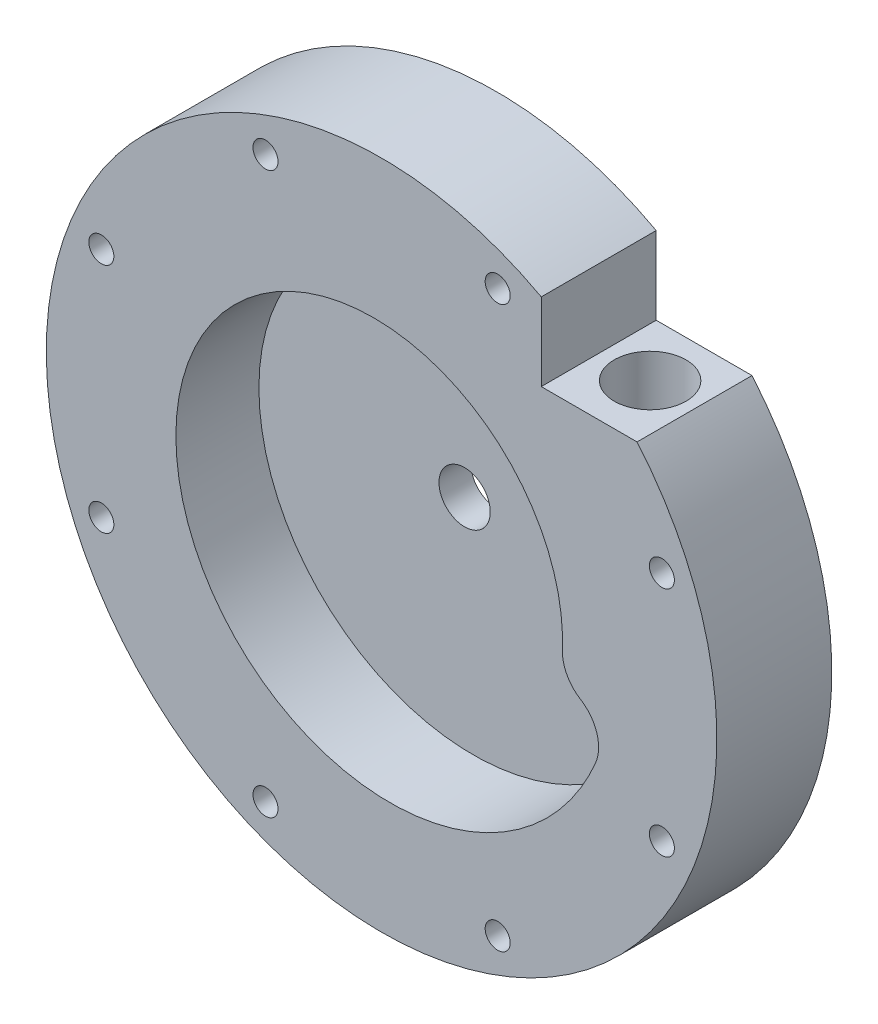
SolidWorks part; units mm, degrees
material "6061-T6 (SS)"
ref_plane "Front Plane" through (0, 0, 0) normal (0, 0, 1) x (1, 0, 0)
ref_plane "Top Plane" through (0, 0, 0) normal (0, 1, 0) x (1, 0, 0)
ref_plane "Right Plane" through (0, 0, 0) normal (1, 0, 0) x (0, 0, -1)
sketch "Sketch22" plane through (0, 0, 0) normal (0, 1, 0) x (1, 0, 0)
  line L0 (-25.4, 0) -> (-5.1, 0)
  line L1 (-25.4, 0) -> (-25.4, -16.51)
  line L2 (-17.4625, 6.35) -> (-17.4625, 4.7625)
  line L3 (-25.4, -16.51) -> (-66.675, -16.51)
  line L4 (-66.675, -16.51) -> (-66.675, 6.35)
  line L9 (-17.4625, 6.35) -> (-66.675, 6.35)
  line L10 (0, 0) -> (0, 9.525) construction
  line L11 (-5.1, 6.35) -> (-5.1, 0)
  line L12 (-17.4625, 4.7625) -> (-11.1125, 4.7625)
  line L15 (-11.1125, 4.7625) -> (-11.1125, 6.35)
  line L16 (-11.1125, 6.35) -> (-5.1, 6.35)
  line L17 (-25.4, -0.508) -> (-0.1653, -0.508) construction
  line L18 (-0.1653, -9.508) -> (-0.1653, -0.508) construction
  dimension "D5" = 50.8
  dimension "D6" = 133.35
  dimension "D7" = 10.2
  dimension "D2" = 6.35
  dimension "D4" = 22.225
  dimension "D8" = 1.5875
  dimension "D1" = 6.35
  dimension "D3" = 22.86
  dimension "D9" = 0.508
revolve "Main Body" add sketch "Sketch22" angle 360 about L10
curve "Volute Spiral"
  spline degree 3 poles (35.9487, 0, 0) (35.9516, 0.0754, 0) (35.9573, 0.2262, 0) (35.9642, 0.4524, 0) (35.9698, 0.6788, 0) (35.9739, 0.9052, 0) (35.9766, 1.1318, 0) (35.9779, 1.3583, 0) (35.9778, 1.585, 0) (35.9763, 1.8117, 0) (35.9733, 2.0385, 0) (35.969, 2.2653, 0) (35.9632, 2.4921, 0) (35.956, 2.7189, 0) (35.9473, 2.9457, 0) (35.9373, 3.1726, 0) (35.9258, 3.3994, 0) (35.9129, 3.6262, 0) (35.8986, 3.853, 0) (35.8828, 4.0798, 0) (35.8656, 4.3065, 0) (35.847, 4.5331, 0) (35.827, 4.7597, 0) (35.8055, 4.9862, 0) (35.7826, 5.2127, 0) (35.7583, 5.439, 0) (35.7326, 5.6653, 0) (35.7054, 5.8914, 0) (35.6768, 6.1174, 0) (35.6468, 6.3433, 0) (35.6153, 6.5691, 0) (35.5825, 6.7947, 0) (35.5482, 7.0201, 0) (35.5124, 7.2455, 0) (35.4753, 7.4706, 0) (35.4367, 7.6955, 0) (35.3967, 7.9203, 0) (35.3553, 8.1449, 0) (35.3125, 8.3692, 0) (35.2683, 8.5934, 0) (35.2226, 8.8173, 0) (35.1755, 9.041, 0) (35.127, 9.2644, 0) (35.0771, 9.4876, 0) (35.0257, 9.7105, 0) (34.973, 9.9332, 0) (34.9188, 10.1556, 0) (34.8633, 10.3777, 0) (34.8063, 10.5995, 0) (34.7479, 10.821, 0) (34.6881, 11.0422, 0) (34.6269, 11.263, 0) (34.5643, 11.4836, 0) (34.5004, 11.7037, 0) (34.435, 11.9236, 0) (34.3682, 12.1431, 0) (34.3, 12.3622, 0) (34.2304, 12.5809, 0) (34.1594, 12.7993, 0) (34.0871, 13.0172, 0) (34.0133, 13.2348, 0) (33.9382, 13.4519, 0) (33.8617, 13.6686, 0) (33.7838, 13.8849, 0) (33.7045, 14.1008, 0) (33.6238, 14.3162, 0) (33.5418, 14.5311, 0) (33.4584, 14.7456, 0) (33.3737, 14.9596, 0) (33.2875, 15.1732, 0) (33.2, 15.3862, 0) (33.1112, 15.5988, 0) (33.021, 15.8108, 0) (32.9294, 16.0223, 0) (32.8365, 16.2333, 0) (32.7422, 16.4438, 0) (32.6466, 16.6537, 0) (32.5497, 16.8631, 0) (32.4514, 17.0719, 0) (32.3517, 17.2801, 0) (32.2508, 17.4878, 0) (32.1485, 17.6949, 0) (32.0448, 17.9013, 0) (31.9399, 18.1072, 0) (31.8336, 18.3125, 0) (31.7261, 18.5171, 0) (31.6172, 18.7212, 0) (31.507, 18.9246, 0) (31.3955, 19.1273, 0) (31.2827, 19.3294, 0) (31.1685, 19.5308, 0) (31.0531, 19.7316, 0) (30.9365, 19.9317, 0) (30.8185, 20.1311, 0) (30.6992, 20.3298, 0) (30.5787, 20.5278, 0) (30.4569, 20.7251, 0) (30.3338, 20.9217, 0) (30.2094, 21.1175, 0) (30.0838, 21.3126, 0) (29.957, 21.507, 0) (29.8288, 21.7006, 0) (29.6995, 21.8935, 0) (29.5689, 22.0856, 0) (29.437, 22.2769, 0) (29.3039, 22.4674, 0) (29.1696, 22.6571, 0) (29.0341, 22.8461, 0) (28.8973, 23.0342, 0) (28.7593, 23.2215, 0) (28.6201, 23.408, 0) (28.4797, 23.5937, 0) (28.3381, 23.7785, 0) (28.1953, 23.9625, 0) (28.0514, 24.1456, 0) (27.9062, 24.3279, 0) (27.7598, 24.5093, 0) (27.6123, 24.6898, 0) (27.4636, 24.8694, 0) (27.3137, 25.0482, 0) (27.1627, 25.226, 0) (27.0105, 25.403, 0) (26.8572, 25.579, 0) (26.7027, 25.7541, 0) (26.5471, 25.9282, 0) (26.3903, 26.1015, 0) (26.2325, 26.2738, 0) (26.0735, 26.4451, 0) (25.9134, 26.6155, 0) (25.7521, 26.7849, 0) (25.5898, 26.9533, 0) (25.4264, 27.1208, 0) (25.2619, 27.2872, 0) (25.0963, 27.4527, 0) (24.9296, 27.6172, 0) (24.7618, 27.7806, 0) (24.593, 27.9431, 0) (24.4231, 28.1045, 0) (24.2521, 28.2649, 0) (24.0802, 28.4242, 0) (23.9071, 28.5825, 0) (23.733, 28.7398, 0) (23.5579, 28.896, 0) (23.3818, 29.0511, 0) (23.2046, 29.2052, 0) (23.0265, 29.3582, 0) (22.8473, 29.5101, 0) (22.6671, 29.6609, 0) (22.486, 29.8106, 0) (22.3038, 29.9592, 0) (22.1207, 30.1067, 0) (21.9366, 30.2531, 0) (21.7515, 30.3984, 0) (21.5655, 30.5425, 0) (21.3785, 30.6855, 0) (21.1906, 30.8274, 0) (21.0018, 30.9681, 0) (20.812, 31.1076, 0) (20.6213, 31.246, 0) (20.4297, 31.3833, 0) (20.2371, 31.5193, 0) (20.0437, 31.6542, 0) (19.8494, 31.7879, 0) (19.6541, 31.9204, 0) (19.458, 32.0517, 0) (19.2611, 32.1818, 0) (19.0632, 32.3106, 0) (18.8645, 32.4383, 0) (18.665, 32.5648, 0) (18.4646, 32.69, 0) (18.2634, 32.814, 0) (18.0613, 32.9368, 0) (17.8584, 33.0583, 0) (17.6547, 33.1786, 0) (17.4502, 33.2976, 0) (17.2449, 33.4154, 0) (17.0389, 33.5319, 0) (16.832, 33.6471, 0) (16.6244, 33.761, 0) (16.4159, 33.8737, 0) (16.2068, 33.9851, 0) (15.9969, 34.0952, 0) (15.7862, 34.204, 0) (15.5748, 34.3115, 0) (15.3627, 34.4177, 0) (15.1498, 34.5226, 0) (14.9363, 34.6262, 0) (14.722, 34.7285, 0) (14.5071, 34.8294, 0) (14.2914, 34.929, 0) (14.0751, 35.0273, 0) (13.8581, 35.1242, 0) (13.6405, 35.2198, 0) (13.4222, 35.3141, 0) (13.2032, 35.407, 0) (12.9836, 35.4985, 0) (12.7634, 35.5887, 0) (12.5426, 35.6775, 0) (12.3212, 35.765, 0) (12.0991, 35.8511, 0) (11.8765, 35.9358, 0) (11.6532, 36.0191, 0) (11.4294, 36.101, 0) (11.205, 36.1816, 0) (10.9801, 36.2607, 0) (10.7546, 36.3385, 0) (10.5286, 36.4148, 0) (10.302, 36.4898, 0) (10.0749, 36.5633, 0) (9.8473, 36.6355, 0) (9.6192, 36.7062, 0) (9.3906, 36.7755, 0) (9.1615, 36.8434, 0) (8.9319, 36.9098, 0) (8.7018, 36.9748, 0) (8.4713, 37.0384, 0) (8.2403, 37.1006, 0) (8.0089, 37.1613, 0) (7.777, 37.2206, 0) (7.5447, 37.2784, 0) (7.312, 37.3348, 0) (7.0789, 37.3897, 0) (6.8453, 37.4432, 0) (6.6114, 37.4952, 0) (6.3771, 37.5458, 0) (6.1424, 37.5949, 0) (5.9074, 37.6425, 0) (5.672, 37.6887, 0) (5.4362, 37.7334, 0) (5.2002, 37.7766, 0) (4.9637, 37.8183, 0) (4.727, 37.8586, 0) (4.49, 37.8974, 0) (4.2526, 37.9347, 0) (4.015, 37.9705, 0) (3.7771, 38.0048, 0) (3.5389, 38.0377, 0) (3.3004, 38.069, 0) (3.0617, 38.0989, 0) (2.8228, 38.1273, 0) (2.5836, 38.1541, 0) (2.3442, 38.1795, 0) (2.1046, 38.2034, 0) (1.8647, 38.2257, 0) (1.6247, 38.2466, 0) (1.3845, 38.2659, 0) (1.1441, 38.2838, 0) (0.9035, 38.3001, 0) (0.6628, 38.315, 0) (0.4219, 38.3283, 0) (0.1808, 38.3401, 0) (-0.0603, 38.3504, 0) (-0.3016, 38.3591, 0) (-0.543, 38.3664, 0) (-0.7845, 38.3721, 0) (-1.0261, 38.3764, 0) (-1.2677, 38.3791, 0) (-1.5095, 38.3802, 0) (-1.7513, 38.3799, 0) (-1.9932, 38.378, 0) (-2.2351, 38.3746, 0) (-2.477, 38.3697, 0) (-2.719, 38.3633, 0) (-2.961, 38.3554, 0) (-3.203, 38.3459, 0) (-3.445, 38.3349, 0) (-3.687, 38.3223, 0) (-3.929, 38.3083, 0) (-4.1709, 38.2927, 0) (-4.4128, 38.2756, 0) (-4.6546, 38.2569, 0) (-4.8964, 38.2368, 0) (-5.1381, 38.2151, 0) (-5.3798, 38.1919, 0) (-5.6213, 38.1671, 0) (-5.8628, 38.1408, 0) (-6.1041, 38.113, 0) (-6.3453, 38.0837, 0) (-6.5864, 38.0529, 0) (-6.8274, 38.0205, 0) (-7.0682, 37.9866, 0) (-7.3089, 37.9512, 0) (-7.5494, 37.9142, 0) (-7.7897, 37.8758, 0) (-8.0298, 37.8358, 0) (-8.2698, 37.7943, 0) (-8.5095, 37.7512, 0) (-8.749, 37.7067, 0) (-8.9883, 37.6606, 0) (-9.2274, 37.613, 0) (-9.4662, 37.5639, 0) (-9.7048, 37.5133, 0) (-9.9431, 37.4612, 0) (-10.1811, 37.4076, 0) (-10.4189, 37.3524, 0) (-10.6563, 37.2957, 0) (-10.8935, 37.2376, 0) (-11.1303, 37.1779, 0) (-11.3669, 37.1167, 0) (-11.6031, 37.054, 0) (-11.8389, 36.9898, 0) (-12.0745, 36.9241, 0) (-12.3096, 36.857, 0) (-12.5444, 36.7883, 0) (-12.7788, 36.7181, 0) (-13.0129, 36.6464, 0) (-13.2465, 36.5733, 0) (-13.4797, 36.4986, 0) (-13.7126, 36.4225, 0) (-13.9449, 36.3449, 0) (-14.1769, 36.2658, 0) (-14.4084, 36.1852, 0) (-14.6395, 36.1032, 0) (-14.8701, 36.0196, 0) (-15.1002, 35.9346, 0) (-15.3299, 35.8482, 0) (-15.559, 35.7602, 0) (-15.7877, 35.6708, 0) (-16.0159, 35.58, 0) (-16.2435, 35.4877, 0) (-16.4706, 35.3939, 0) (-16.6972, 35.2987, 0) (-16.9232, 35.202, 0) (-17.1487, 35.1039, 0) (-17.3736, 35.0043, 0) (-17.5979, 34.9033, 0) (-17.8217, 34.8009, 0) (-18.0448, 34.697, 0) (-18.2674, 34.5917, 0) (-18.4893, 34.485, 0) (-18.7107, 34.3769, 0) (-18.9314, 34.2673, 0) (-19.1514, 34.1563, 0) (-19.3708, 34.044, 0) (-19.5896, 33.9302, 0) (-19.8077, 33.815, 0) (-20.0251, 33.6984, 0) (-20.2419, 33.5804, 0) (-20.4579, 33.461, 0) (-20.6733, 33.3402, 0) (-20.8879, 33.218, 0) (-21.1018, 33.0945, 0) (-21.315, 32.9696, 0) (-21.5275, 32.8433, 0) (-21.7392, 32.7156, 0) (-21.9501, 32.5866, 0) (-22.1603, 32.4562, 0) (-22.3698, 32.3245, 0) (-22.5784, 32.1914, 0) (-22.7863, 32.057, 0) (-22.9933, 31.9212, 0) (-23.1996, 31.7841, 0) (-23.405, 31.6457, 0) (-23.6097, 31.5059, 0) (-23.8134, 31.3648, 0) (-24.0164, 31.2224, 0) (-24.2185, 31.0787, 0) (-24.4197, 30.9337, 0) (-24.6201, 30.7874, 0) (-24.8196, 30.6398, 0) (-25.0182, 30.4909, 0) (-25.216, 30.3407, 0) (-25.4128, 30.1892, 0) (-25.6087, 30.0365, 0) (-25.8037, 29.8825, 0) (-25.9978, 29.7272, 0) (-26.191, 29.5707, 0) (-26.3832, 29.4129, 0) (-26.5745, 29.2539, 0) (-26.7648, 29.0936, 0) (-26.9541, 28.9321, 0) (-27.1425, 28.7693, 0) (-27.3299, 28.6054, 0) (-27.5163, 28.4402, 0) (-27.7017, 28.2738, 0) (-27.8861, 28.1062, 0) (-28.0695, 27.9374, 0) (-28.2519, 27.7674, 0) (-28.4332, 27.5962, 0) (-28.6135, 27.4238, 0) (-28.7928, 27.2503, 0) (-28.971, 27.0756, 0) (-29.1482, 26.8997, 0) (-29.3243, 26.7227, 0) (-29.4993, 26.5445, 0) (-29.6733, 26.3652, 0) (-29.8461, 26.1847, 0) (-30.0179, 26.0031, 0) (-30.1885, 25.8204, 0) (-30.3581, 25.6366, 0) (-30.5265, 25.4516, 0) (-30.6938, 25.2656, 0) (-30.86, 25.0784, 0) (-31.025, 24.8902, 0) (-31.1889, 24.7009, 0) (-31.3516, 24.5105, 0) (-31.5132, 24.319, 0) (-31.6736, 24.1265, 0) (-31.8329, 23.9329, 0) (-31.9909, 23.7382, 0) (-32.1478, 23.5426, 0) (-32.3034, 23.3459, 0) (-32.4579, 23.1481, 0) (-32.6112, 22.9494, 0) (-32.7632, 22.7496, 0) (-32.914, 22.5489, 0) (-33.0636, 22.3471, 0) (-33.212, 22.1443, 0) (-33.3591, 21.9406, 0) (-33.505, 21.7359, 0) (-33.6496, 21.5302, 0) (-33.7929, 21.3236, 0) (-33.935, 21.116, 0) (-34.0758, 20.9075, 0) (-34.2154, 20.698, 0) (-34.3536, 20.4876, 0) (-34.4906, 20.2763, 0) (-34.6262, 20.0641, 0) (-34.7606, 19.851, 0) (-34.8936, 19.637, 0) (-35.0253, 19.4221, 0) (-35.1557, 19.2063, 0) (-35.2848, 18.9896, 0) (-35.4126, 18.7721, 0) (-35.539, 18.5537, 0) (-35.664, 18.3345, 0) (-35.7877, 18.1144, 0) (-35.9101, 17.8935, 0) (-36.0311, 17.6718, 0) (-36.1507, 17.4493, 0) (-36.2689, 17.2259, 0) (-36.3858, 17.0018, 0) (-36.5013, 16.7769, 0) (-36.6154, 16.5512, 0) (-36.7281, 16.3247, 0) (-36.8394, 16.0975, 0) (-36.9493, 15.8695, 0) (-37.0578, 15.6408, 0) (-37.1649, 15.4113, 0) (-37.2705, 15.1811, 0) (-37.3748, 14.9502, 0) (-37.4776, 14.7186, 0) (-37.5789, 14.4862, 0) (-37.6789, 14.2532, 0) (-37.7773, 14.0195, 0) (-37.8744, 13.7851, 0) (-37.97, 13.5501, 0) (-38.0641, 13.3144, 0) (-38.1567, 13.078, 0) (-38.2479, 12.8411, 0) (-38.3377, 12.6034, 0) (-38.4259, 12.3652, 0) (-38.5127, 12.1264, 0) (-38.598, 11.8869, 0) (-38.6818, 11.6469, 0) (-38.7641, 11.4062, 0) (-38.8449, 11.165, 0) (-38.9242, 10.9233, 0) (-39.002, 10.6809, 0) (-39.0783, 10.4381, 0) (-39.1531, 10.1947, 0) (-39.2264, 9.9507, 0) (-39.2982, 9.7063, 0) (-39.3684, 9.4613, 0) (-39.4371, 9.2159, 0) (-39.5043, 8.9699, 0) (-39.57, 8.7235, 0) (-39.6341, 8.4766, 0) (-39.6966, 8.2292, 0) (-39.7577, 7.9814, 0) (-39.8172, 7.7332, 0) (-39.8751, 7.4845, 0) (-39.9315, 7.2354, 0) (-39.9863, 6.9858, 0) (-40.0396, 6.7359, 0) (-40.0913, 6.4856, 0) (-40.1414, 6.2349, 0) (-40.19, 5.9838, 0) (-40.237, 5.7324, 0) (-40.2825, 5.4806, 0) (-40.3263, 5.2284, 0) (-40.3686, 4.976, 0) (-40.4093, 4.7232, 0) (-40.4484, 4.47, 0) (-40.486, 4.2166, 0) (-40.5219, 3.9629, 0) (-40.5563, 3.7089, 0) (-40.5891, 3.4546, 0) (-40.6203, 3.2001, 0) (-40.6498, 2.9453, 0) (-40.6778, 2.6902, 0) (-40.7042, 2.435, 0) (-40.729, 2.1795, 0) (-40.7522, 1.9237, 0) (-40.7738, 1.6678, 0) (-40.7937, 1.4117, 0) (-40.8121, 1.1554, 0) (-40.8289, 0.8989, 0) (-40.844, 0.6423, 0) (-40.8575, 0.3855, 0) (-40.8695, 0.1285, 0) (-40.8798, -0.1286, 0) (-40.8884, -0.3858, 0) (-40.8955, -0.6431, 0) (-40.901, -0.9005, 0) (-40.9048, -1.158, 0) (-40.907, -1.4156, 0) (-40.9076, -1.6733, 0) (-40.9066, -1.931, 0) (-40.9039, -2.1888, 0) (-40.8996, -2.4467, 0) (-40.8937, -2.7045, 0) (-40.8862, -2.9624, 0) (-40.8771, -3.2203, 0) (-40.8663, -3.4782, 0) (-40.8539, -3.7361, 0) (-40.8399, -3.994, 0) (-40.8242, -4.2519, 0) (-40.8069, -4.5097, 0) (-40.788, -4.7674, 0) (-40.7675, -5.0251, 0) (-40.7453, -5.2828, 0) (-40.7215, -5.5403, 0) (-40.6961, -5.7978, 0) (-40.669, -6.0552, 0) (-40.6404, -6.3124, 0) (-40.6101, -6.5695, 0) (-40.5781, -6.8265, 0) (-40.5446, -7.0834, 0) (-40.5094, -7.3401, 0) (-40.4726, -7.5967, 0) (-40.4342, -7.853, 0) (-40.3941, -8.1092, 0) (-40.3525, -8.3652, 0) (-40.3092, -8.621, 0) (-40.2643, -8.8766, 0) (-40.2177, -9.1319, 0) (-40.1696, -9.3871, 0) (-40.1198, -9.6419, 0) (-40.0684, -9.8966, 0) (-40.0154, -10.1509, 0) (-39.9608, -10.405, 0) (-39.9046, -10.6588, 0) (-39.8468, -10.9123, 0) (-39.7873, -11.1655, 0) (-39.7263, -11.4184, 0) (-39.6636, -11.6709, 0) (-39.5994, -11.9232, 0) (-39.5335, -12.175, 0) (-39.466, -12.4265, 0) (-39.397, -12.6777, 0) (-39.3263, -12.9285, 0) (-39.254, -13.1789, 0) (-39.1802, -13.4288, 0) (-39.1048, -13.6784, 0) (-39.0277, -13.9276, 0) (-38.9491, -14.1763, 0) (-38.8689, -14.4246, 0) (-38.7871, -14.6725, 0) (-38.7038, -14.9199, 0) (-38.6188, -15.1668, 0) (-38.5323, -15.4132, 0) (-38.4442, -15.6592, 0) (-38.3546, -15.9047, 0) (-38.2634, -16.1496, 0) (-38.1706, -16.3941, 0) (-38.0762, -16.638, 0) (-37.9803, -16.8813, 0) (-37.8829, -17.1242, 0) (-37.7839, -17.3664, 0) (-37.6833, -17.6081, 0) (-37.5812, -17.8492, 0) (-37.4776, -18.0898, 0) (-37.3724, -18.3297, 0) (-37.2657, -18.569, 0) (-37.1574, -18.8077, 0) (-37.0477, -19.0458, 0) (-36.9364, -19.2833, 0) (-36.8236, -19.5201, 0) (-36.7092, -19.7562, 0) (-36.5934, -19.9917, 0) (-36.476, -20.2265, 0) (-36.3572, -20.4606, 0) (-36.2368, -20.694, 0) (-36.1149, -20.9268, 0) (-35.9916, -21.1588, 0) (-35.8667, -21.3901, 0) (-35.7404, -21.6206, 0) (-35.6126, -21.8504, 0) (-35.4833, -22.0795, 0) (-35.3526, -22.3078, 0) (-35.2203, -22.5353, 0) (-35.0867, -22.762, 0) (-34.9515, -22.988, 0) (-34.8149, -23.2131, 0) (-34.6769, -23.4375, 0) (-34.5374, -23.661, 0) (-34.3964, -23.8837, 0) (-34.2541, -24.1056, 0) (-34.1103, -24.3266, 0) (-33.9651, -24.5468, 0) (-33.8184, -24.7661, 0) (-33.6704, -24.9845, 0) (-33.5209, -25.202, 0) (-33.3701, -25.4187, 0) (-33.2178, -25.6345, 0) (-33.0641, -25.8493, 0) (-32.9091, -26.0632, 0) (-32.7527, -26.2762, 0) (-32.5949, -26.4883, 0) (-32.4357, -26.6994, 0) (-32.2751, -26.9096, 0) (-32.1132, -27.1188, 0) (-31.95, -27.327, 0) (-31.7854, -27.5343, 0) (-31.6194, -27.7405, 0) (-31.4522, -27.9458, 0) (-31.2835, -28.15, 0) (-31.1136, -28.3533, 0) (-30.9424, -28.5555, 0) (-30.7698, -28.7567, 0) (-30.5959, -28.9568, 0) (-30.4207, -29.1559, 0) (-30.2443, -29.354, 0) (-30.0665, -29.5509, 0) (-29.8875, -29.7468, 0) (-29.7072, -29.9417, 0) (-29.5256, -30.1354, 0) (-29.3428, -30.328, 0) (-29.1587, -30.5195, 0) (-28.9733, -30.7099, 0) (-28.7867, -30.8992, 0) (-28.5989, -31.0874, 0) (-28.4099, -31.2744, 0) (-28.2196, -31.4602, 0) (-28.0281, -31.6449, 0) (-27.8354, -31.8285, 0) (-27.6416, -32.0109, 0) (-27.4465, -32.1921, 0) (-27.2502, -32.3721, 0) (-27.0528, -32.5509, 0) (-26.8542, -32.7285, 0) (-26.6544, -32.9049, 0) (-26.4535, -33.0801, 0) (-26.2514, -33.254, 0) (-26.0482, -33.4267, 0) (-25.8438, -33.5982, 0) (-25.6383, -33.7685, 0) (-25.4317, -33.9374, 0) (-25.224, -34.1052, 0) (-25.0152, -34.2716, 0) (-24.8053, -34.4368, 0) (-24.5943, -34.6007, 0) (-24.3822, -34.7633, 0) (-24.1691, -34.9246, 0) (-23.9549, -35.0846, 0) (-23.7396, -35.2432, 0) (-23.5233, -35.4006, 0) (-23.3059, -35.5566, 0) (-23.0876, -35.7113, 0) (-22.8681, -35.8647, 0) (-22.6477, -36.0167, 0) (-22.4263, -36.1674, 0) (-22.2039, -36.3167, 0) (-21.9804, -36.4646, 0) (-21.756, -36.6112, 0) (-21.5306, -36.7564, 0) (-21.3043, -36.9002, 0) (-21.077, -37.0426, 0) (-20.8488, -37.1836, 0) (-20.6196, -37.3232, 0) (-20.3894, -37.4614, 0) (-20.1584, -37.5981, 0) (-19.9264, -37.7335, 0) (-19.6936, -37.8674, 0) (-19.4598, -37.9999, 0) (-19.2252, -38.1309, 0) (-18.9897, -38.2605, 0) (-18.7533, -38.3886, 0) (-18.516, -38.5153, 0) (-18.2779, -38.6405, 0) (-18.039, -38.7643, 0) (-17.7992, -38.8866, 0) (-17.5586, -39.0073, 0) (-17.3172, -39.1266, 0) (-17.075, -39.2444, 0) (-16.8319, -39.3607, 0) (-16.5881, -39.4755, 0) (-16.3436, -39.5888, 0) (-16.0982, -39.7006, 0) (-15.8521, -39.8109, 0) (-15.6052, -39.9196, 0) (-15.3576, -40.0268, 0) (-15.1093, -40.1325, 0) (-14.8602, -40.2366, 0) (-14.6105, -40.3392, 0) (-14.36, -40.4402, 0) (-14.1088, -40.5397, 0) (-13.857, -40.6377, 0) (-13.6045, -40.734, 0) (-13.3513, -40.8288, 0) (-13.0975, -40.922, 0) (-12.843, -41.0137, 0) (-12.5879, -41.1037, 0) (-12.3321, -41.1922, 0) (-12.0758, -41.2791, 0) (-11.8188, -41.3644, 0) (-11.5613, -41.4481, 0) (-11.3031, -41.5302, 0) (-11.0444, -41.6106, 0) (-10.7851, -41.6895, 0) (-10.5253, -41.7668, 0) (-10.2649, -41.8424, 0) (-10.004, -41.9164, 0) (-9.7426, -41.9888, 0) (-9.4806, -42.0596, 0) (-9.2182, -42.1287, 0) (-8.9552, -42.1962, 0) (-8.6918, -42.262, 0) (-8.4279, -42.3262, 0) (-8.1635, -42.3888, 0) (-7.8987, -42.4497, 0) (-7.6334, -42.509, 0) (-7.3677, -42.5666, 0) (-7.1016, -42.6225, 0) (-6.835, -42.6768, 0) (-6.5681, -42.7294, 0) (-6.3007, -42.7803, 0) (-6.033, -42.8296, 0) (-5.7649, -42.8772, 0) (-5.4965, -42.9231, 0) (-5.2277, -42.9673, 0) (-4.9586, -43.0099, 0) (-4.6891, -43.0508, 0) (-4.4194, -43.0899, 0) (-4.1493, -43.1274, 0) (-3.8789, -43.1632, 0) (-3.6082, -43.1973, 0) (-3.3373, -43.2298, 0) (-3.0661, -43.2605, 0) (-2.7946, -43.2895, 0) (-2.5229, -43.3168, 0) (-2.251, -43.3424, 0) (-1.9788, -43.3663, 0) (-1.7064, -43.3885, 0) (-1.4339, -43.4089, 0) (-1.1611, -43.4277, 0) (-0.8882, -43.4448, 0) (-0.615, -43.4601, 0) (-0.3418, -43.4737, 0) (-0.0684, -43.4856, 0) (0.2052, -43.4958, 0) (0.4789, -43.5043, 0) (0.7527, -43.511, 0) (1.0266, -43.516, 0) (1.3005, -43.5193, 0) (1.5746, -43.5209, 0) (1.8488, -43.5208, 0) (2.123, -43.5189, 0) (2.3972, -43.5153, 0) (2.6715, -43.5099, 0) (2.9458, -43.5029, 0) (3.2201, -43.4941, 0) (3.4945, -43.4836, 0) (3.7688, -43.4713, 0) (4.0431, -43.4574, 0) (4.3174, -43.4417, 0) (4.5917, -43.4242, 0) (4.8659, -43.405, 0) (5.1401, -43.3841, 0) (5.4141, -43.3615, 0) (5.6881, -43.3372, 0) (5.962, -43.3111, 0) (6.2358, -43.2832, 0) (6.5095, -43.2537, 0) (6.7831, -43.2224, 0) (7.0565, -43.1894, 0) (7.3298, -43.1547, 0) (7.6029, -43.1182, 0) (7.8759, -43.08, 0) (8.1486, -43.0401, 0) (8.4212, -42.9984, 0) (8.6936, -42.955, 0) (8.9658, -42.9099, 0) (9.2377, -42.8631, 0) (9.5094, -42.8146, 0) (9.7809, -42.7643, 0) (10.0521, -42.7123, 0) (10.3231, -42.6586, 0) (10.5937, -42.6032, 0) (10.8641, -42.546, 0) (11.1342, -42.4872, 0) (11.4039, -42.4266, 0) (11.6734, -42.3643, 0) (11.9425, -42.3003, 0) (12.2113, -42.2346, 0) (12.4797, -42.1672, 0) (12.7477, -42.0981, 0) (13.0154, -42.0273, 0) (13.2827, -41.9548, 0) (13.5496, -41.8805, 0) (13.8161, -41.8046, 0) (14.0822, -41.727, 0) (14.3478, -41.6477, 0) (14.613, -41.5667, 0) (14.8777, -41.4841, 0) (15.142, -41.3997, 0) (15.4058, -41.3136, 0) (15.6692, -41.2259, 0) (15.932, -41.1365, 0) (16.1943, -41.0454, 0) (16.4562, -40.9527, 0) (16.7174, -40.8583, 0) (16.9782, -40.7622, 0) (17.2384, -40.6644, 0) (17.498, -40.565, 0) (17.7571, -40.4639, 0) (18.0156, -40.3612, 0) (18.2735, -40.2568, 0) (18.5309, -40.1508, 0) (18.7876, -40.0432, 0) (19.0436, -39.9339, 0) (19.2991, -39.8229, 0) (19.5539, -39.7104, 0) (19.808, -39.5962, 0) (20.0615, -39.4803, 0) (20.3144, -39.3629, 0) (20.5665, -39.2438, 0) (20.8179, -39.1231, 0) (21.0687, -39.0008, 0) (21.3187, -38.877, 0) (21.568, -38.7515, 0) (21.8166, -38.6244, 0) (22.0644, -38.4957, 0) (22.3114, -38.3654, 0) (22.5577, -38.2335, 0) (22.8033, -38.1001, 0) (23.048, -37.9651, 0) (23.2919, -37.8285, 0) (23.5351, -37.6903, 0) (23.7774, -37.5506, 0) (24.0189, -37.4094, 0) (24.2595, -37.2665, 0) (24.4993, -37.1222, 0) (24.7383, -36.9762, 0) (24.9764, -36.8288, 0) (25.2136, -36.6798, 0) (25.4499, -36.5293, 0) (25.6854, -36.3773, 0) (25.9199, -36.2237, 0) (26.1535, -36.0687, 0) (26.3862, -35.9121, 0) (26.6179, -35.7541, 0) (26.8487, -35.5945, 0) (27.0786, -35.4335, 0) (27.3075, -35.271, 0) (27.5354, -35.1069, 0) (27.7623, -34.9415, 0) (27.9883, -34.7745, 0) (28.2132, -34.6061, 0) (28.4372, -34.4363, 0) (28.6601, -34.265, 0) (28.882, -34.0923, 0) (29.1028, -33.9181, 0) (29.3226, -33.7425, 0) (29.5413, -33.5655, 0) (29.759, -33.387, 0) (29.9756, -33.2072, 0) (30.1911, -33.0259, 0) (30.4055, -32.8433, 0) (30.6188, -32.6592, 0) (30.831, -32.4738, 0) (31.0421, -32.287, 0) (31.2521, -32.0988, 0) (31.4609, -31.9093, 0) (31.6686, -31.7184, 0) (31.8751, -31.5261, 0) (32.0804, -31.3326, 0) (32.2846, -31.1376, 0) (32.4876, -30.9414, 0) (32.6894, -30.7438, 0) (32.89, -30.5449, 0) (33.0894, -30.3447, 0) (33.2875, -30.1433, 0) (33.4845, -29.9405, 0) (33.6802, -29.7364, 0) (33.8747, -29.5311, 0) (34.0679, -29.3244, 0) (34.2599, -29.1166, 0) (34.4506, -28.9074, 0) (34.64, -28.6971, 0) (34.8281, -28.4855, 0) (35.015, -28.2726, 0) (35.2005, -28.0585, 0) (35.3848, -27.8433, 0) (35.5677, -27.6268, 0) (35.7493, -27.4091, 0) (35.9296, -27.1902, 0) (36.1085, -26.9701, 0) (36.2861, -26.7489, 0) (36.4623, -26.5265, 0) (36.6372, -26.3029, 0) (36.8107, -26.0782, 0) (36.9828, -25.8523, 0) (37.1536, -25.6254, 0) (37.3229, -25.3972, 0) (37.4909, -25.168, 0) (37.6574, -24.9377, 0) (37.8226, -24.7062, 0) (37.9863, -24.4737, 0) (38.1486, -24.2401, 0) (38.3094, -24.0054, 0) (38.4688, -23.7697, 0) (38.6268, -23.5329, 0) (38.7833, -23.295, 0) (38.9383, -23.0561, 0) (39.0919, -22.8162, 0) (39.2439, -22.5753, 0) (39.3945, -22.3333, 0) (39.5437, -22.0904, 0) (39.6913, -21.8465, 0) (39.8374, -21.6015, 0) (39.982, -21.3557, 0) (40.1251, -21.1088, 0) (40.2666, -20.861, 0) (40.4067, -20.6122, 0) (40.5452, -20.3625, 0) (40.6821, -20.1119, 0) (40.8175, -19.8604, 0) (40.9514, -19.6079, 0) (41.0837, -19.3546, 0) (41.2144, -19.1004, 0) (41.3436, -18.8453, 0) (41.4711, -18.5893, 0) (41.5971, -18.3325, 0) (41.7215, -18.0748, 0) (41.8444, -17.8162, 0) (41.9656, -17.5569, 0) (42.0852, -17.2967, 0) (42.2031, -17.0357, 0) (42.3195, -16.7739, 0) (42.4343, -16.5114, 0) (42.5474, -16.248, 0) (42.6589, -15.9839, 0) (42.7687, -15.719, 0) (42.8769, -15.4534, 0) (42.9835, -15.187, 0) (43.0884, -14.9199, 0) (43.1916, -14.6521, 0) (43.2932, -14.3836, 0) (43.3931, -14.1144, 0) (43.4913, -13.8444, 0) (43.5879, -13.5739, 0) (43.6828, -13.3026, 0) (43.776, -13.0307, 0) (43.8675, -12.7581, 0) (43.9573, -12.4849, 0) (44.0454, -12.2111, 0) (44.1318, -11.9367, 0) (44.2164, -11.6617, 0) (44.2994, -11.386, 0) (44.3807, -11.1098, 0) (44.4602, -10.833, 0) (44.538, -10.5557, 0) (44.6141, -10.2778, 0) (44.6884, -9.9994, 0) (44.761, -9.7204, 0) (44.8319, -9.4409, 0) (44.901, -9.1609, 0) (44.9684, -8.8805, 0) (45.034, -8.5995, 0) (45.0979, -8.3181, 0) (45.16, -8.0362, 0) (45.2204, -7.7538, 0) (45.279, -7.471, 0) (45.3358, -7.1878, 0) (45.3908, -6.9041, 0) (45.4441, -6.6201, 0) (45.4956, -6.3356, 0) (45.5453, -6.0508, 0) (45.5932, -5.7656, 0) (45.6394, -5.48, 0) (45.6837, -5.1941, 0) (45.7263, -4.9078, 0) (45.7671, -4.6212, 0) (45.8061, -4.3343, 0) (45.8432, -4.0471, 0) (45.8786, -3.7596, 0) (45.9122, -3.4717, 0) (45.944, -3.1837, 0) (45.9739, -2.8953, 0) (46.0021, -2.6067, 0) (46.0284, -2.3179, 0) (46.053, -2.0288, 0) (46.0757, -1.7396, 0) (46.0966, -1.4501, 0) (46.1157, -1.1604, 0) (46.133, -0.8705, 0) (46.1484, -0.5805, 0) (46.1621, -0.2903, 0) (46.1697, -0.0968, 0) (46.1735, 0, 0) knots 0 0 0 0 0.000879 0.001759 0.002638 0.003518 0.004398 0.005279 0.006159 0.00704 0.007921 0.008802 0.009684 0.010565 0.011447 0.012329 0.013212 0.014094 0.014977 0.01586 0.016744 0.017627 0.018511 0.019395 0.020279 0.021163 0.022048 0.022933 0.023818 0.024703 0.025589 0.026475 0.027361 0.028247 0.029133 0.03002 0.030907 0.031794 0.032681 0.033569 0.034457 0.035345 0.036233 0.037122 0.03801 0.038899 0.039789 0.040678 0.041568 0.042458 0.043348 0.044238 0.045129 0.04602 0.046911 0.047802 0.048693 0.049585 0.050477 0.051369 0.052262 0.053154 0.054047 0.05494 0.055834 0.056727 0.057621 0.058515 0.05941 0.060304 0.061199 0.062094 0.062989 0.063884 0.06478 0.065676 0.066572 0.067469 0.068365 0.069262 0.070159 0.071056 0.071954 0.072852 0.07375 0.074648 0.075546 0.076445 0.077344 0.078243 0.079143 0.080042 0.080942 0.081842 0.082743 0.083643 0.084544 0.085445 0.086346 0.087248 0.08815 0.089052 0.089954 0.090856 0.091759 0.092662 0.093565 0.094468 0.095372 0.096276 0.09718 0.098084 0.098989 0.099894 0.100799 0.101704 0.102609 0.103515 0.104421 0.105327 0.106234 0.10714 0.108047 0.108954 0.109862 0.110769 0.111677 0.112585 0.113494 0.114402 0.115311 0.11622 0.117129 0.118039 0.118948 0.119858 0.120769 0.121679 0.12259 0.123501 0.124412 0.125323 0.126235 0.127147 0.128059 0.128971 0.129884 0.130797 0.13171 0.132623 0.133536 0.13445 0.135364 0.136278 0.137193 0.138108 0.139023 0.139938 0.140853 0.141769 0.142685 0.143601 0.144517 0.145434 0.146351 0.147268 0.148185 0.149103 0.15002 0.150938 0.151857 0.152775 0.153694 0.154613 0.155532 0.156452 0.157371 0.158291 0.159212 0.160132 0.161053 0.161974 0.162895 0.163816 0.164738 0.16566 0.166582 0.167504 0.168427 0.169349 0.170272 0.171196 0.172119 0.173043 0.173967 0.174891 0.175816 0.176741 0.177666 0.178591 0.179516 0.180442 0.181368 0.182294 0.18322 0.184147 0.185074 0.186001 0.186928 0.187856 0.188784 0.189712 0.19064 0.191569 0.192498 0.193427 0.194356 0.195286 0.196215 0.197145 0.198076 0.199006 0.199937 0.200868 0.201799 0.20273 0.203662 0.204594 0.205526 0.206459 0.207391 0.208324 0.209257 0.210191 0.211124 0.212058 0.212992 0.213927 0.214861 0.215796 0.216731 0.217667 0.218602 0.219538 0.220474 0.22141 0.222347 0.223284 0.224221 0.225158 0.226095 0.227033 0.227971 0.228909 0.229848 0.230787 0.231726 0.232665 0.233604 0.234544 0.235484 0.236424 0.237364 0.238305 0.239246 0.240187 0.241128 0.24207 0.243012 0.243954 0.244896 0.245839 0.246782 0.247725 0.248668 0.249612 0.250556 0.2515 0.252444 0.253389 0.254333 0.255278 0.256224 0.257169 0.258115 0.259061 0.260007 0.260954 0.2619 0.262847 0.263795 0.264742 0.26569 0.266638 0.267586 0.268534 0.269483 0.270432 0.271381 0.272331 0.27328 0.27423 0.27518 0.276131 0.277081 0.278032 0.278983 0.279935 0.280886 0.281838 0.28279 0.283743 0.284695 0.285648 0.286601 0.287555 0.288508 0.289462 0.290416 0.29137 0.292325 0.29328 0.294235 0.29519 0.296146 0.297102 0.298058 0.299014 0.29997 0.300927 0.301884 0.302841 0.303799 0.304757 0.305715 0.306673 0.307631 0.30859 0.309549 0.310508 0.311468 0.312428 0.313388 0.314348 0.315308 0.316269 0.31723 0.318191 0.319152 0.320114 0.321076 0.322038 0.323001 0.323963 0.324926 0.325889 0.326853 0.327817 0.32878 0.329745 0.330709 0.331674 0.332639 0.333604 0.334569 0.335535 0.336501 0.337467 0.338433 0.3394 0.340367 0.341334 0.342301 0.343269 0.344237 0.345205 0.346173 0.347142 0.34811 0.34908 0.350049 0.351019 0.351988 0.352958 0.353929 0.354899 0.35587 0.356841 0.357813 0.358784 0.359756 0.360728 0.3617 0.362673 0.363646 0.364619 0.365592 0.366566 0.367539 0.368514 0.369488 0.370462 0.371437 0.372412 0.373388 0.374363 0.375339 0.376315 0.377291 0.378268 0.379245 0.380222 0.381199 0.382176 0.383154 0.384132 0.38511 0.386089 0.387068 0.388047 0.389026 0.390006 0.390985 0.391965 0.392946 0.393926 0.394907 0.395888 0.396869 0.397851 0.398833 0.399815 0.400797 0.401779 0.402762 0.403745 0.404728 0.405712 0.406696 0.40768 0.408664 0.409648 0.410633 0.411618 0.412603 0.413589 0.414575 0.415561 0.416547 0.417534 0.41852 0.419507 0.420495 0.421482 0.42247 0.423458 0.424446 0.425435 0.426423 0.427412 0.428402 0.429391 0.430381 0.431371 0.432361 0.433352 0.434343 0.435334 0.436325 0.437316 0.438308 0.4393 0.440292 0.441285 0.442278 0.443271 0.444264 0.445258 0.446251 0.447245 0.44824 0.449234 0.450229 0.451224 0.452219 0.453215 0.454211 0.455207 0.456203 0.457199 0.458196 0.459193 0.460191 0.461188 0.462186 0.463184 0.464182 0.465181 0.46618 0.467179 0.468178 0.469177 0.470177 0.471177 0.472178 0.473178 0.474179 0.47518 0.476181 0.477183 0.478185 0.479187 0.480189 0.481192 0.482195 0.483198 0.484201 0.485205 0.486209 0.487213 0.488217 0.489222 0.490226 0.491232 0.492237 0.493243 0.494248 0.495255 0.496261 0.497267 0.498274 0.499281 0.500289 0.501297 0.502304 0.503313 0.504321 0.50533 0.506338 0.507348 0.508357 0.509367 0.510377 0.511387 0.512397 0.513408 0.514419 0.51543 0.516441 0.517453 0.518465 0.519477 0.52049 0.521502 0.522515 0.523528 0.524542 0.525556 0.52657 0.527584 0.528598 0.529613 0.530628 0.531643 0.532659 0.533674 0.53469 0.535707 0.536723 0.53774 0.538757 0.539774 0.540792 0.54181 0.542828 0.543846 0.544864 0.545883 0.546902 0.547921 0.548941 0.549961 0.550981 0.552001 0.553022 0.554043 0.555064 0.556085 0.557107 0.558128 0.559151 0.560173 0.561196 0.562218 0.563241 0.564265 0.565288 0.566312 0.567336 0.568361 0.569386 0.57041 0.571436 0.572461 0.573487 0.574513 0.575539 0.576565 0.577592 0.578619 0.579646 0.580673 0.581701 0.582729 0.583757 0.584786 0.585815 0.586844 0.587873 0.588902 0.589932 0.590962 0.591992 0.593023 0.594054 0.595085 0.596116 0.597147 0.598179 0.599211 0.600244 0.601276 0.602309 0.603342 0.604375 0.605409 0.606443 0.607477 0.608511 0.609546 0.610581 0.611616 0.612651 0.613687 0.614723 0.615759 0.616795 0.617832 0.618869 0.619906 0.620943 0.621981 0.623019 0.624057 0.625096 0.626134 0.627173 0.628213 0.629252 0.630292 0.631332 0.632372 0.633413 0.634453 0.635494 0.636536 0.637577 0.638619 0.639661 0.640703 0.641746 0.642789 0.643832 0.644875 0.645919 0.646963 0.648007 0.649051 0.650096 0.651141 0.652186 0.653231 0.654277 0.655323 0.656369 0.657415 0.658462 0.659509 0.660556 0.661604 0.662651 0.663699 0.664748 0.665796 0.666845 0.667894 0.668943 0.669993 0.671042 0.672092 0.673143 0.674193 0.675244 0.676295 0.677346 0.678398 0.67945 0.680502 0.681554 0.682607 0.68366 0.684713 0.685766 0.68682 0.687874 0.688928 0.689982 0.691037 0.692092 0.693147 0.694203 0.695258 0.696314 0.697371 0.698427 0.699484 0.700541 0.701598 0.702656 0.703713 0.704771 0.70583 0.706888 0.707947 0.709006 0.710066 0.711125 0.712185 0.713245 0.714305 0.715366 0.716427 0.717488 0.71855 0.719611 0.720673 0.721735 0.722798 0.72386 0.724923 0.725987 0.72705 0.728114 0.729178 0.730242 0.731307 0.732371 0.733436 0.734502 0.735567 0.736633 0.737699 0.738766 0.739832 0.740899 0.741966 0.743033 0.744101 0.745169 0.746237 0.747306 0.748374 0.749443 0.750512 0.751582 0.752652 0.753722 0.754792 0.755862 0.756933 0.758004 0.759075 0.760147 0.761219 0.762291 0.763363 0.764436 0.765508 0.766582 0.767655 0.768729 0.769802 0.770877 0.771951 0.773026 0.774101 0.775176 0.776251 0.777327 0.778403 0.779479 0.780556 0.781632 0.782709 0.783787 0.784864 0.785942 0.78702 0.788098 0.789177 0.790256 0.791335 0.792414 0.793494 0.794574 0.795654 0.796734 0.797815 0.798896 0.799977 0.801058 0.80214 0.803222 0.804304 0.805387 0.806469 0.807552 0.808636 0.809719 0.810803 0.811887 0.812971 0.814056 0.815141 0.816226 0.817311 0.818397 0.819483 0.820569 0.821655 0.822742 0.823829 0.824916 0.826004 0.827091 0.828179 0.829268 0.830356 0.831445 0.832534 0.833623 0.834713 0.835803 0.836893 0.837983 0.839074 0.840165 0.841256 0.842347 0.843439 0.844531 0.845623 0.846715 0.847808 0.848901 0.849994 0.851088 0.852181 0.853275 0.85437 0.855464 0.856559 0.857654 0.858749 0.859845 0.860941 0.862037 0.863133 0.86423 0.865327 0.866424 0.867521 0.868619 0.869717 0.870815 0.871914 0.873013 0.874112 0.875211 0.87631 0.87741 0.87851 0.879611 0.880711 0.881812 0.882913 0.884014 0.885116 0.886218 0.88732 0.888423 0.889525 0.890628 0.891732 0.892835 0.893939 0.895043 0.896147 0.897252 0.898356 0.899461 0.900567 0.901672 0.902778 0.903884 0.904991 0.906097 0.907204 0.908311 0.909419 0.910527 0.911635 0.912743 0.913851 0.91496 0.916069 0.917178 0.918288 0.919398 0.920508 0.921618 0.922729 0.92384 0.924951 0.926062 0.927174 0.928286 0.929398 0.93051 0.931623 0.932736 0.933849 0.934963 0.936077 0.937191 0.938305 0.93942 0.940534 0.941649 0.942765 0.94388 0.944996 0.946113 0.947229 0.948346 0.949463 0.95058 0.951697 0.952815 0.953933 0.955051 0.95617 0.957289 0.958408 0.959527 0.960647 0.961767 0.962887 0.964007 0.965128 0.966249 0.96737 0.968491 0.969613 0.970735 0.971857 0.97298 0.974103 0.975226 0.976349 0.977473 0.978596 0.979721 0.980845 0.98197 0.983094 0.98422 0.985345 0.986471 0.987597 0.988723 0.98985 0.990976 0.992103 0.993231 0.994358 0.995486 0.996614 0.997742 0.998871 1 1 1 1
sketch "Sketch23" plane through (0, 0, 0) normal (0, 0, 1) x (1, 0, 0)
  arc A9 (39.5526, -6.7699) -> (42.554, -16.2316) centre (35.542, -13.249) cw
  arc A10 (39.5526, -6.7699) -> (35.9487, 0) centre (43.5632, -0.2907) cw
  spline S1 degree 3 poles (2032.2967, -112.9679) (24.3117, -28.1062) (35.5238, -14.0537) (35.9642, 0.4524) (35.9698, 0.6788) (35.978, 1.1318) (35.9808, 2.1906) (35.9203, 3.7799) (35.7473, 5.6682) (35.4899, 7.4743) (35.1415, 9.2689) (34.7024, 11.0474) (34.1734, 12.8052) (33.5555, 14.5378) (32.8499, 16.2406) (32.0579, 17.9093) (31.1812, 19.5395) (30.2217, 21.1268) (29.1814, 22.6671) (28.0626, 24.1562) (26.8679, 25.5901) (25.6, 26.965) (24.2618, 28.2771) (22.8563, 29.5228) (21.3869, 30.6987) (19.8571, 31.8015) (18.2704, 32.828) (16.6307, 33.7754) (14.9419, 34.6409) (13.2081, 35.422) (11.4336, 36.1163) (9.6226, 36.7217) (7.7796, 37.2362) (5.9092, 37.6583) (4.016, 37.9864) (2.1048, 38.2193) (0.1803, 38.3561) (-1.7527, 38.3959) (-3.6892, 38.3382) (-5.6243, 38.1829) (-7.5532, 37.9299) (-9.4708, 37.5794) (-11.3722, 37.132) (-13.2527, 36.5883) (-15.1071, 35.9494) (-16.9308, 35.2164) (-18.719, 34.3909) (-20.467, 33.4746) (-22.1701, 32.4694) (-23.8239, 31.3775) (-25.4239, 30.2014) (-26.9658, 28.9437) (-28.4455, 27.6072) (-29.859, 26.1951) (-31.2023, 24.7106) (-32.4718, 23.1572) (-33.664, 21.5386) (-34.7754, 19.8587) (-35.803, 18.1214) (-36.7437, 16.3309) (-37.5948, 14.4916) (-38.3539, 12.6081) (-39.0185, 10.6848) (-39.5866, 8.7265) (-40.0564, 6.7381) (-40.4263, 4.7245) (-40.6948, 2.6907) (-40.861, 0.6418) (-40.9241, -1.4169) (-40.8833, -3.4804) (-40.7384, -5.5433) (-40.4894, -7.6005) (-40.1364, -9.6466) (-39.68, -11.6765) (-39.1208, -13.6848) (-38.46, -15.6664) (-37.6987, -17.6161) (-36.8386, -19.5288) (-35.8813, -21.3996) (-34.8291, -23.2234) (-33.684, -24.9955) (-32.4488, -26.7111) (-31.1261, -28.3656) (-29.7191, -29.9546) (-28.2309, -31.4738) (-26.665, -32.919) (-25.0251, -34.2863) (-23.3151, -35.5718) (-21.539, -36.772) (-19.7012, -37.8835) (-17.806, -38.9031) (-15.8581, -39.8277) (-13.8621, -40.6548) (-11.8231, -41.3818) (-9.7459, -42.0065) (-7.6359, -42.5268) (-5.4981, -42.9411) (-3.338, -43.2478) (-1.1609, -43.4458) (1.0277, -43.5342) (3.2222, -43.5122) (5.4171, -43.3795) (7.6068, -43.136) (9.7857, -42.782) (11.9482, -42.3178) (14.0887, -41.7442) (16.2017, -41.0623) (18.2818, -40.2733) (20.3235, -39.379) (22.3214, -38.381) (24.2702, -37.2817) (26.165, -36.0833) (28.0005, -34.7886) (29.7719, -33.4005) (31.4745, -31.9221) (33.1036, -30.3569) (34.6549, -28.7085) (36.124, -26.9808) (37.5069, -25.1779) (38.7998, -23.3041) (39.999, -21.3639) (41.1011, -19.362) (42.103, -17.3033) (43.0016, -15.1927) (43.7944, -13.0354) (44.4789, -10.8369) (45.0529, -8.6024) (45.5146, -6.3376) (45.8479, -4.1437) (46.0176, -2.5105) (46.0902, -1.5466) (46.1157, -1.1604) (46.133, -0.8705) (46.1484, -0.5805) (46.9534, 16.4404) (35.9358, 33.8664) (2045.3238, -34.5738) knots -0.166508 -0.166508 -0.166508 -0.166508 0.000879 0.001759 0.002638 0.003518 0.00704 0.014977 0.022048 0.029133 0.036233 0.043348 0.050477 0.057621 0.06478 0.071954 0.079143 0.086346 0.093565 0.100799 0.108047 0.115311 0.12259 0.129884 0.137193 0.144517 0.151857 0.159212 0.166582 0.173967 0.181368 0.188784 0.196215 0.203662 0.211124 0.218602 0.226095 0.233604 0.241128 0.248668 0.256224 0.263795 0.271381 0.278983 0.286601 0.294235 0.301884 0.309549 0.31723 0.324926 0.332639 0.340367 0.34811 0.35587 0.363646 0.371437 0.379245 0.387068 0.394907 0.402762 0.410633 0.41852 0.426423 0.434343 0.442278 0.450229 0.458196 0.46618 0.474179 0.482195 0.490226 0.498274 0.506338 0.514419 0.522515 0.530628 0.538757 0.546902 0.555064 0.563241 0.571436 0.579646 0.587873 0.596116 0.604375 0.612651 0.620943 0.629252 0.637577 0.645919 0.654277 0.662651 0.671042 0.67945 0.687874 0.696314 0.704771 0.713245 0.721735 0.730242 0.738766 0.747306 0.755862 0.764436 0.773026 0.781632 0.790256 0.798896 0.807552 0.816226 0.824916 0.833623 0.842347 0.851088 0.859845 0.868619 0.87741 0.886218 0.895043 0.903884 0.912743 0.921618 0.93051 0.93942 0.948346 0.957289 0.966249 0.975226 0.98422 0.992103 0.994358 0.995486 0.996614 0.997742 0.998871 1.195214 1.195214 1.195214 1.195214 only from (35.9487, 0) to (46.1735, 0) construction
  spline S2 degree 3 poles (35.9487, 0) (35.9516, 0.0754) (35.9573, 0.2262) (35.9642, 0.4524) (35.9698, 0.6788) (35.978, 1.1318) (35.9808, 2.1906) (35.9203, 3.7799) (35.7473, 5.6682) (35.4899, 7.4743) (35.1415, 9.2689) (34.7024, 11.0474) (34.1734, 12.8052) (33.5555, 14.5378) (32.8499, 16.2406) (32.0579, 17.9093) (31.1812, 19.5395) (30.2217, 21.1268) (29.1814, 22.6671) (28.0626, 24.1562) (26.8679, 25.5901) (25.6, 26.965) (24.2618, 28.2771) (22.8563, 29.5228) (21.3869, 30.6987) (19.8571, 31.8015) (18.2704, 32.828) (16.6307, 33.7754) (14.9419, 34.6409) (13.2081, 35.422) (11.4336, 36.1163) (9.6226, 36.7217) (7.7796, 37.2362) (5.9092, 37.6583) (4.016, 37.9864) (2.1048, 38.2193) (0.1803, 38.3561) (-1.7527, 38.3959) (-3.6892, 38.3382) (-5.6243, 38.1829) (-7.5532, 37.9299) (-9.4708, 37.5794) (-11.3722, 37.132) (-13.2527, 36.5883) (-15.1071, 35.9494) (-16.9308, 35.2164) (-18.719, 34.3909) (-20.467, 33.4746) (-22.1701, 32.4694) (-23.8239, 31.3775) (-25.4239, 30.2014) (-26.9658, 28.9437) (-28.4455, 27.6072) (-29.859, 26.1951) (-31.2023, 24.7106) (-32.4718, 23.1572) (-33.664, 21.5386) (-34.7754, 19.8587) (-35.803, 18.1214) (-36.7437, 16.3309) (-37.5948, 14.4916) (-38.3539, 12.6081) (-39.0185, 10.6848) (-39.5866, 8.7265) (-40.0564, 6.7381) (-40.4263, 4.7245) (-40.6948, 2.6907) (-40.861, 0.6418) (-40.9241, -1.4169) (-40.8833, -3.4804) (-40.7384, -5.5433) (-40.4894, -7.6005) (-40.1364, -9.6466) (-39.68, -11.6765) (-39.1208, -13.6848) (-38.46, -15.6664) (-37.6987, -17.6161) (-36.8386, -19.5288) (-35.8813, -21.3996) (-34.8291, -23.2234) (-33.684, -24.9955) (-32.4488, -26.7111) (-31.1261, -28.3656) (-29.7191, -29.9546) (-28.2309, -31.4738) (-26.665, -32.919) (-25.0251, -34.2863) (-23.3151, -35.5718) (-21.539, -36.772) (-19.7012, -37.8835) (-17.806, -38.9031) (-15.8581, -39.8277) (-13.8621, -40.6548) (-11.8231, -41.3818) (-9.7459, -42.0065) (-7.6359, -42.5268) (-5.4981, -42.9411) (-3.338, -43.2478) (-1.1609, -43.4458) (1.0277, -43.5342) (3.2222, -43.5122) (5.4171, -43.3795) (7.6068, -43.136) (9.7857, -42.782) (11.9482, -42.3178) (14.0887, -41.7442) (16.2017, -41.0623) (18.2818, -40.2733) (20.3235, -39.379) (22.3214, -38.381) (24.2702, -37.2817) (26.165, -36.0833) (28.0005, -34.7886) (29.7719, -33.4005) (31.4745, -31.9221) (33.1036, -30.3569) (34.6549, -28.7085) (36.124, -26.9808) (37.5069, -25.1779) (38.7998, -23.3041) (39.999, -21.3639) (41.1011, -19.362) (42.103, -17.3033) (43.0016, -15.1927) (43.7944, -13.0354) (44.4789, -10.8369) (45.0529, -8.6024) (45.5146, -6.3376) (45.8479, -4.1437) (46.0176, -2.5105) (46.0902, -1.5466) (46.1157, -1.1604) (46.133, -0.8705) (46.1484, -0.5805) (46.1621, -0.2903) (46.1697, -0.0968) (46.1735, 0) knots 0 0 0 0 0.000879 0.001759 0.002638 0.003518 0.00704 0.014977 0.022048 0.029133 0.036233 0.043348 0.050477 0.057621 0.06478 0.071954 0.079143 0.086346 0.093565 0.100799 0.108047 0.115311 0.12259 0.129884 0.137193 0.144517 0.151857 0.159212 0.166582 0.173967 0.181368 0.188784 0.196215 0.203662 0.211124 0.218602 0.226095 0.233604 0.241128 0.248668 0.256224 0.263795 0.271381 0.278983 0.286601 0.294235 0.301884 0.309549 0.31723 0.324926 0.332639 0.340367 0.34811 0.35587 0.363646 0.371437 0.379245 0.387068 0.394907 0.402762 0.410633 0.41852 0.426423 0.434343 0.442278 0.450229 0.458196 0.46618 0.474179 0.482195 0.490226 0.498274 0.506338 0.514419 0.522515 0.530628 0.538757 0.546902 0.555064 0.563241 0.571436 0.579646 0.587873 0.596116 0.604375 0.612651 0.620943 0.629252 0.637577 0.645919 0.654277 0.662651 0.671042 0.67945 0.687874 0.696314 0.704771 0.713245 0.721735 0.730242 0.738766 0.747306 0.755862 0.764436 0.773026 0.781632 0.790256 0.798896 0.807552 0.816226 0.824916 0.833623 0.842347 0.851088 0.859845 0.868619 0.87741 0.886218 0.895043 0.903884 0.912743 0.921618 0.93051 0.93942 0.948346 0.957289 0.966249 0.975226 0.98422 0.992103 0.994358 0.995486 0.996614 0.997742 0.998871 1 1 1 1
  dimension "D1" = 7.62
extrude "Volute Cut" cut sketch "Sketch23" along normal through all contours S2 | S2 region at (-0.2832, -3.2433, 0)
sketch "Sketch28" plane through (0, 0, 16.51) normal (0, 0, 1) x (1, 0, 0)
  line L1 (31.75, 58.6301) -> (50.804, 58.6301)
  line L2 (31.75, 58.6301) -> (31.75, 43.18)
  line L3 (31.75, 43.18) -> (50.804, 43.18)
  line L4 (50.804, 58.6301) -> (50.804, 43.18)
  circle A1 centre (0, 0) radius 66.675 construction
  dimension "D1" = 43.18
  dimension "D2" = 31.75
extrude "Outlet Hole Cut" cut sketch "Sketch28" against normal through all
hole_wizard "Outlet Hole" positions "3DSketch2" profile "Sketch20" hole size "W" standard "ANSI Inch"
sketch3d "3DSketch2"
  line L1 (0, 0, 0) -> (41.529, 0, 0) construction
  line L2 (41.529, 0, 0) -> (41.529, 0, 9.2753) construction
  point P22 (41.529, 43.18, 4.6377)
  point P70 (41.529, 0, 4.6377)
  dimension "D1" = 9.2753
  dimension "D2" = 41.529
sketch "Sketch20" plane through (41.529, 43.18, 4.6377) normal (1, 0, 0) x (0, 0, 1)
  line L0 (0, 0) -> (0, 58.8255)
  line L1 (0, 58.8255) -> (4.9022, 55.88)
  line L2 (4.9022, 55.88) -> (4.9022, 0)
  line L5 (4.9022, 0) -> (0, 0)
  line L10 (0, 58.8255) -> (-4.9022, 55.88) construction
  line L11 (0, -6.35) -> (0, 107.95) construction
  dimension "Hole Dia." = 9.8044
  dimension "Hole Depth" = 55.88
  dimension "Drill Angle" = 118
hole_wizard "Outlet NPT" positions "3DSketch4" profile "Sketch29" hole size "3/8" standard "ANSI Inch"
sketch3d "3DSketch4"
  circle A0 centre (41.529, 43.18, 4.6377) radius 4.9022 construction
  point P0 (41.529, 43.18, 4.6377)
  point P6 (41.529, 48.0822, 4.6377)
sketch "Sketch29" plane through (41.529, 43.18, 4.6377) normal (1, 0, 0) x (0, 0, 1)
  line L0 (0, 0) -> (0, 16.9886)
  line L1 (0, 16.9886) -> (7.1374, 12.7)
  line L2 (7.1374, 12.7) -> (7.1374, 0)
  line L5 (7.1374, 0) -> (0, 0)
  line L10 (0, 16.9886) -> (-7.1374, 12.7) construction
  line L11 (0, -6.35) -> (0, 107.95) construction
  dimension "Hole Dia." = 14.2748
  dimension "Hole Depth" = 12.7
  dimension "Drill Angle" = 118
hole_wizard "Fastener Holes" positions "3DSketch5" profile "Sketch30" hole size "#10" standard "ANSI Inch" end condition through all
sketch3d "3DSketch5"
  line L0 (0, 0, 0) -> (0, 0, 16.51) construction
  line L1 (0, 0, 16.51) -> (66.675, 0, 16.51) construction
  line L3 (0, 0, 16.51) -> (55.733, -23.0854, 16.51) construction
  circle A0 centre (0, 0, 16.51) radius 66.675 construction
  point P0 (55.733, -23.0854, 16.51)
  point P15 (0, 0, 83.185)
  dimension "D1" = 22.5
  dimension "D2" = 60.325
sketch "Sketch30" plane through (55.733, -23.0854, 16.51) normal (1, 0, 0) x (0, -1, 0)
  line L0 (0, 0) -> (0, 22.86)
  line L1 (0, 22.86) -> (2.4892, 22.86)
  line L2 (2.4892, 22.86) -> (2.4892, 0)
  line L5 (2.4892, 0) -> (0, 0)
  line L11 (0, -6.35) -> (0, 107.95) construction
  dimension "Thru Hole Dia." = 4.9784
  dimension "Thru Hole Depth" = 22.86
pattern_circular "CirPattern1" count 8 over 360 about axis through (0, 0, 0) along (0, 0, 1) of "Fastener Holes" reverse direction yes
equation "\"D7@Sketch22\"=10.2/25.4"
equation "\"D9@Sketch22\"=\"Fluid Clearance@[TP] [Pump] [Ox] Pump.Assembly\""
equation "\"D1@Sketch22\"=\"Volute Floor Thickness@[TP] [Pump] [Ox] Pump.Assembly\""
equation "\"D6@Sketch22\"=\"Casing OD@[TP] [Pump] [Ox] Pump.Assembly\""
equation "\"D3@Sketch22\" = \"Volute Casing Height@[TP] [Pump] [Ox] Pump.Assembly\""
equation "\"D1@3DSketch2\"=\"Volute Height@[TP] [Pump] [Ox] Pump.Assembly\""
equation "\"D2@3DSketch2\"=\"Outlet Radial Position@[TP] [Pump] [Ox] Pump.Assembly\""
